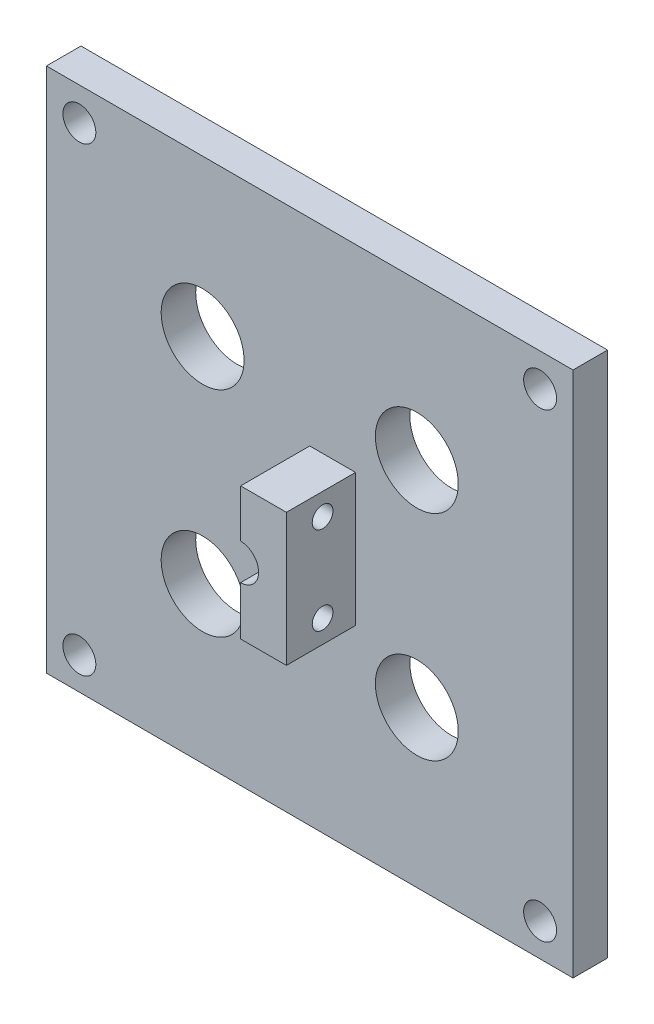
SolidWorks part; units mm, degrees
material "Pure Gold"
ref_plane "Front" through (0, 0, 0) normal (0, 0, 1) x (1, 0, 0)
ref_plane "Top" through (0, 0, 0) normal (0, 1, 0) x (1, 0, 0)
ref_plane "Right" through (0, 0, 0) normal (1, 0, 0) x (0, 0, -1)
sketch "Sketch4" plane through (0, 0, 0) normal (0, 0, 1) x (1, 0, 0)
  line L0 (0, -42.8625) -> (0, 41.275) construction
  line L1 (-49.15, -15.5) -> (-80.15, 15.5) construction
  line L2 (-80.15, -15.5) -> (-49.15, 15.5) construction
  line L3 (-39.925, 44.5615) -> (-39.925, -66.5635) construction
  line L4 (-71.275, 44.5615) -> (-71.275, -66.5635) construction
  line L8 (-62.05, 15.5) -> (-31.05, -15.5) construction
  line L9 (-31.05, 15.5) -> (-62.05, -15.5) construction
  line L11 (-31.05, 36.624) -> (-31.05, -53.8635) construction
  line L12 (43.75, 0) -> (-164.4633, 0) construction
  line L13 (-62.05, 36.624) -> (-62.05, -53.8635) construction
  line L14 (-49.15, 36.624) -> (-49.15, -53.8635) construction
  line L15 (-80.15, 36.624) -> (-80.15, -53.8635) construction
  line L16 (-113.2228, 15.5) -> (-0.2036, 15.5) construction
  line L17 (-113.2228, -15.5) -> (-0.2036, -15.5) construction
  line L18 (-25, -66.5635) -> (-25, 44.5615) construction
  line L19 (-68.1, -66.5635) -> (-68.1, 44.5615) construction
  line L20 (-43.1, 44.5615) -> (-43.1, -66.5635) construction
  line L21 (-86.2, -66.5635) -> (-86.2, 44.5615) construction
  line L22 (5.8397, -21.55) -> (-134.1626, -21.55) construction
  line L23 (5.8397, 21.55) -> (-134.1626, 21.55) construction
  line L24 (10.9249, -24.725) -> (-138.6228, -24.725) construction
  line L25 (10.9249, 24.725) -> (-138.6228, 24.725) construction
  line L26 (-89.375, 44.5615) -> (-89.375, -66.5635) construction
  line L27 (-21.825, 44.5615) -> (-21.825, -66.5635) construction
  circle A0 centre (0, 0) radius 12.7 construction
  circle A1 centre (0, 0) radius 15.875 construction
  circle A2 centre (0, 0) radius 9.46 construction
  circle A3 centre (-93.65, 0) radius 9.46 construction
  arc A4 (-93.65, 12.7) -> (-93.65, -12.7) centre (-93.65, 0) ccw construction
  circle A5 centre (27.27, 0) radius 9.46 construction
  circle A6 centre (27.27, 0) radius 12.7 construction
  circle A7 centre (-120.3675, 0) radius 9.46 construction
  circle A8 centre (-120.3675, 0) radius 12.7 construction
  point P3 (0, 0)
  point P6 (-49.15, -15.5)
  point P11 (-93.65, 0)
  point P12 (-49.15, 15.5)
  point P13 (-46.55, 0)
  point P14 (-80.15, 15.5)
  point P15 (-80.15, -15.5)
  point P61 (-64.65, 0)
  point P65 (27.27, 0)
  point P66 (-120.3675, 0)
  dimension "D20" = 3.175
  dimension "D18" = 29
  dimension "D26" = 73.82
  dimension "D27" = 64.65
  dimension "D2" = 31
  dimension "D3" = 25
  dimension "D4" = 31
  dimension "D5" = 21.825
  dimension "D6" = 15.5
  dimension "D7" = 15.5
  dimension "D8" = 6.05
  dimension "D9" = 6.05
  dimension "D10" = 6.05
  dimension "D11" = 6.05
  dimension "D12" = 6.05
  dimension "D13" = 6.05
  dimension "D14" = 3.175
  dimension "D15" = 3.175
  dimension "D16" = 3.175
  dimension "D17" = 3.175
  dimension "D19" = 3.175
  dimension "D21" = 3.175
  dimension "D22" = 46.55
  dimension "D23" = 47.1
  dimension "D24" = 58.32
  dimension "D25" = 147.6375
sketch "Sketch5" plane through (0, 0, 0) normal (0, 0, 1) x (1, 0, 0)
  line L0 (-46.55, 1.6) -> (-46.55, -2.6) construction
  line L4 (-46.55, -2.6) -> (-46.55, -9.6636)
  line L5 (-46.55, 9.525) -> (-39.925, 9.525)
  line L7 (-39.925, 44.5615) -> (-39.925, -66.5635) construction
  line L8 (-39.925, -9.6636) -> (-39.925, 9.525)
  line L9 (-46.55, -9.6636) -> (-39.925, -9.6636)
  line L13 (-46.55, 9.525) -> (-46.55, 2.6)
  circle A0 centre (-46.55, 0) radius 2.6 construction
  arc A1 (-46.55, 2.6) -> (-46.55, -2.6) centre (-46.55, 0) cw
extrude "Extrude1" add sketch "Sketch5" along normal blind 10
sketch "Sketch6" plane through (0, 0, 0) normal (0, 0, -1) x (-1, 0, 0)
  line L0 (13.2125, 50.8) -> (13.2125, -98.425) construction
  line L1 (79.8875, 63.5) -> (79.8875, -95.3388) construction
  line L2 (84.65, 61.9125) -> (84.65, -95.25) construction
  line L3 (8.45, 55.5625) -> (8.45, -109.5375) construction
  line L4 (125.4125, 33.3375) -> (-41.8258, 33.3375) construction
  line L5 (123.825, 38.1) -> (-50.9969, 38.1) construction
  line L6 (119.0625, -38.1) -> (-36.5125, -38.1) construction
  line L7 (119.0625, -33.3375) -> (-42.8625, -33.3375) construction
  line L9 (84.65, 38.1) -> (8.45, 38.1)
  line L10 (84.65, 38.1) -> (84.65, -37.9954)
  line L11 (84.65, -37.9954) -> (8.45, -38.1)
  line L12 (8.45, 38.1) -> (8.45, -38.1)
  circle A0 centre (79.8875, -33.3375) radius 2.3813
  circle A1 centre (13.2125, -33.3375) radius 2.3812
  circle A2 centre (13.2125, 33.3375) radius 2.3812
  circle A3 centre (79.8875, 33.3375) radius 2.3813
  circle A4 centre (46.55, 0) radius 2.6
  circle A5 centre (31.05, -15.5) radius 6
  circle A6 centre (62.05, -15.5) radius 6
  circle A7 centre (31.05, 15.5) radius 6
  circle A8 centre (62.05, 15.5) radius 6
  dimension "D1" = 38.1
  dimension "D2" = 4.7625
  dimension "D3" = 38.1
  dimension "D4" = 4.7625
  dimension "D5" = 38.1
  dimension "D6" = 38.1
  dimension "D7" = 4.7625
  dimension "D8" = 4.7625
extrude "Extrude2" add sketch "Sketch6" along normal blind 5
sketch "Sketch7" plane through (-39.925, 0, 0) normal (1, 0, 0) x (0, 0, -1)
  circle A0 centre (-4.7625, 6.35) radius 1.5
  circle A1 centre (-4.7625, -6.35) radius 1.5
extrude "Extrude3" cut sketch "Sketch7" against normal up to surface (6.625 mm away) up to face at (-46.55, 6.9281, 6.25)
